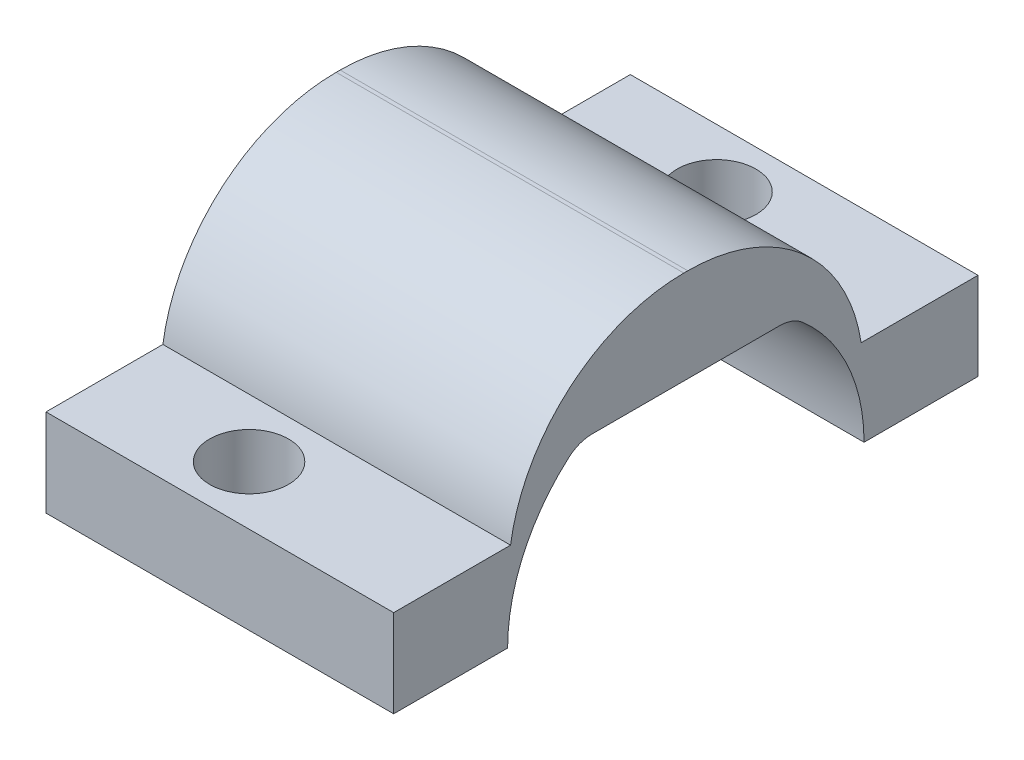
SolidWorks part; units mm, degrees
ref_plane "Plano frontal" through (0, 0, 0) normal (0, 0, 1) x (1, 0, 0)
ref_plane "Plano superior" through (0, 0, 0) normal (0, 1, 0) x (1, 0, 0)
ref_plane "Plano direito" through (0, 0, 0) normal (1, 0, 0) x (0, 0, -1)
sketch "Esboço1" plane through (0, 0, 0) normal (1, 0, 0) x (0, 0, -1)
  line L0 (0, -6.1) -> (0, -5.1)
  line L1 (0, 6.1) -> (0, 4.9)
  line L2 (-6.1, 0) -> (6.1, 0)
  line L3 (-3.6332, 4.9) -> (3.6332, 4.9)
  line L4 (-6.1, 0) -> (-10, 0)
  line L5 (6.1, 0) -> (10, 0)
  line L6 (-10, 0) -> (-10, 3)
  line L7 (10, 0) -> (10, 3)
  line L8 (-10, 3) -> (-6, 3)
  line L9 (-6, 3) -> (-6, 8.1)
  line L10 (-6, 8.1) -> (6, 8.1)
  line L11 (10, 3) -> (6, 3)
  line L12 (6, 3) -> (6, 8.1)
  circle A0 centre (0, 0) radius 6.1
  point P12 (0, 4.9)
  dimension "D1" = 12.2
  dimension "D2" = 1.2
  dimension "D3" = 1
  dimension "D4" = 3.9
  dimension "D5" = 3.9
  dimension "D6" = 3
  dimension "D7" = 3
  dimension "D8" = 2
extrude "Ressalto-extrusão1" add sketch "Esboço1" along normal blind 13.9 contours A0 L5 L7 L11 L12 L10 L9 L8 L6 L4 | L1 A0 L3 | L3 A0 L1 region at (0, 5.3843, -1.3823) region at (0, 5.9971, 1.9808) region at (0, 5.3843, 1.3823)
fillet "Filete1" radius 6 2 edges at (6.95, 8.1, 6) (6.95, 8.1, -6)
sketch "Esboço2" plane through (0, 3, 0) normal (0, 1, 0) x (1, 0, 0)
  line L0 (6.95, -6) -> (6.95, -10)
  line L1 (13.9, -6) -> (0, -6) construction
  line L2 (13.9, -10) -> (0, -10) construction
  line L3 (6.95, 6) -> (6.95, 10)
  line L4 (13.9, 6) -> (0, 6) construction
  line L5 (13.9, 10) -> (0, 10) construction
  circle A0 centre (6.95, 8) radius 1.35
  circle A1 centre (6.95, -8) radius 1.35
  dimension "D1" = 2.7
  dimension "D2" = 2.7
extrude "Corte-extrusão1" cut sketch "Esboço2" against normal blind 13.9 contours L3 A0 | L3 A0 | L0 A1 | L0 A1 region at (7.523, 3, 8) region at (6.377, 3, 8) region at (6.377, 3, -8) region at (7.523, 3, -8)
fillet "Filete2" radius 1.2 2 edges at (6.95, 4.9, -3.6332) (6.95, 4.9, 3.6332)
sketch "Esboço3" plane through (0, 3, 0) normal (0, 1, 0) x (1, 0, 0)
  line L0 (0, 10) -> (2, 10)
  line L1 (0, 10) -> (0, -10.0535)
  line L2 (2, 10) -> (2, -10.0535)
  line L3 (0, -10.0535) -> (2, -10.0535)
  line L4 (13.9, 10) -> (0, 10) construction
  dimension "D1" = 2
extrude "Corte-extrusão2" cut sketch "Esboço3" against normal through all both and the other way through all
sketch "Esboço4" plane through (2, 0, 0) normal (-1, 0, 0) x (0, 0, 1)
  line L0 (-10, 0) -> (-10, 0.25)
  line L1 (-10, 0) -> (10.133, 0)
  line L2 (-10, 0.25) -> (10.133, 0.25)
  line L3 (10.133, 0) -> (10.133, 0.25)
  line L4 (-10, 0) -> (-10, 3) construction
  dimension "D1" = 0.25
